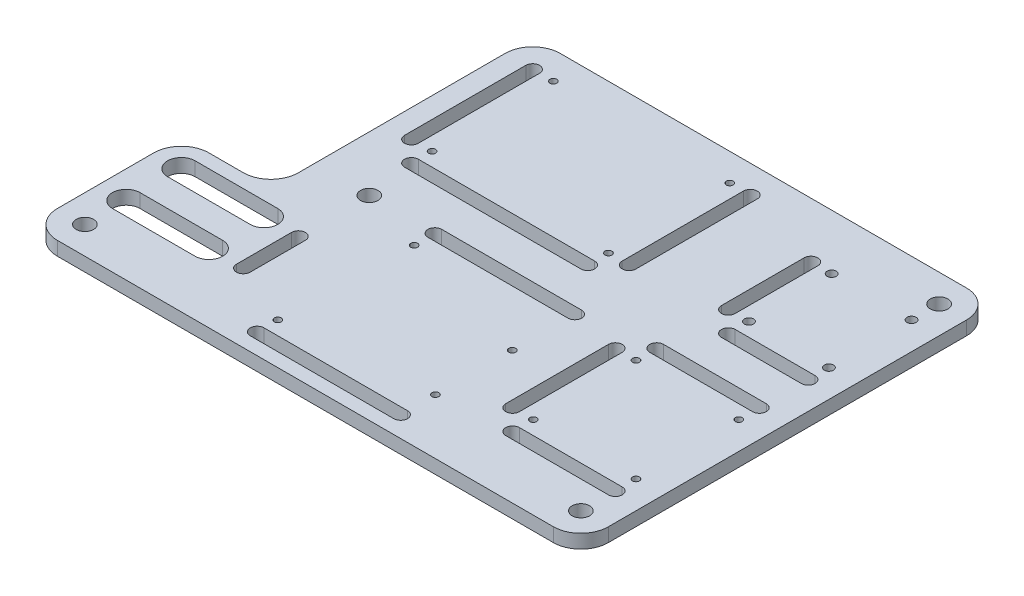
SolidWorks part; units mm, degrees
ref_plane "Front Plane" through (0, 0, 0) normal (0, 0, 1) x (1, 0, 0)
ref_plane "Top Plane" through (0, 0, 0) normal (0, 1, 0) x (1, 0, 0)
ref_plane "Right Plane" through (0, 0, 0) normal (1, 0, 0) x (0, 0, -1)
sketch "Sketch1" plane through (0, 0, 0) normal (0, 1, 0) x (1, 0, 0)
  line L1 (-90, -75) -> (90, -75)
  line L2 (-100, -65) -> (-100, 65)
  line L3 (-90, 75) -> (90, 75)
  line L4 (100, -65) -> (100, 65)
  line L5 (-100, -75) -> (100, 75) construction
  line L6 (-100, 75) -> (100, -75) construction
  arc A0 (90, -75) -> (100, -65) centre (90, -65) ccw
  arc A1 (-90, -75) -> (-100, -65) centre (-90, -65) cw
  arc A2 (-100, 65) -> (-90, 75) centre (-90, 65) cw
  arc A3 (90, 75) -> (100, 65) centre (90, 65) cw
  point P1 (0, 0)
  dimension "D3" = 10
  dimension "D1" = 200
  dimension "D2" = 150
extrude "Boss-Extrude1" add sketch "Sketch1" along normal blind 5 contours L2 A2 L3 A3 L4 A0 L1 A1
hole_wizard "arduino uno holes" positions "Sketch3" profile "Sketch2" tap size "M3x0.5" standard "ANSI Metric" end condition through all
sketch "Sketch3" plane through (0, 5, 0) normal (0, 1, 0) x (1, 0, 0)
  line L0 (-90, -75) -> (90, -75) construction
  line L1 (-100, -65) -> (-100, 65) construction
  point P0 (27.1, -27)
  point P2 (27.1, -54.9)
  point P4 (-23.7, -11.8)
  point P6 (-25, -60)
  dimension "D1" = 27.9
  dimension "D2" = 15.2
  dimension "D3" = 50.8
  dimension "D4" = 1.3
  dimension "D5" = 5.1
  dimension "D6" = 15
  dimension "D7" = 75
sketch "Sketch2" plane through (27.1, 5, 27) normal (1, 0, 0) x (0, 0, 1)
  line L0 (0, 0) -> (0, 5)
  line L1 (0, 5) -> (1.25, 5)
  line L2 (1.25, 5) -> (1.25, 0)
  line L5 (1.25, 0) -> (0, 0)
  line L11 (0, -6.35) -> (0, 107.95) construction
  dimension "Thru Tap Drill Dia." = 2.5
  dimension "Thru Tap Drill Depth" = 5
cosmetic thread "Hole Thread1" parameters "D2"=3
cosmetic thread "Hole Thread2" parameters "D2"=3
cosmetic thread "Hole Thread3" parameters "D2"=3
cosmetic thread "Hole Thread4" parameters "D2"=3
hole_wizard "l298n holes" positions "Sketch16" profile "Sketch17" tap size "M3x0.5" standard "ANSI Metric" end condition through all
sketch "Sketch16" plane through (0, 5, 0) normal (0, 1, 0) x (1, 0, 0)
  line L0 (100, -65) -> (100, 65) construction
  line L1 (-90, -75) -> (90, -75) construction
  point P0 (52.7, -45)
  point P6 (90, -45)
  point P7 (90, -7.7)
  point P8 (52.7, -7.7)
  dimension "D3" = 10
  dimension "D4" = 30
  dimension "D5" = 37.3
  dimension "D6" = 37.3
  dimension "D1" = 2
  dimension "D2" = 2
sketch "Sketch17" plane through (52.7, 5, 45) normal (1, 0, 0) x (0, 0, 1)
  line L0 (0, 0) -> (0, 5)
  line L1 (0, 5) -> (1.25, 5)
  line L2 (1.25, 5) -> (1.25, 0)
  line L5 (1.25, 0) -> (0, 0)
  line L11 (0, -6.35) -> (0, 107.95) construction
  dimension "Thru Tap Drill Dia." = 2.5
  dimension "Thru Tap Drill Depth" = 5
cosmetic thread "Hole Thread25" parameters "D2"=3
cosmetic thread "Hole Thread26" parameters "D2"=3
cosmetic thread "Hole Thread27" parameters "D2"=3
cosmetic thread "Hole Thread28" parameters "D2"=3
hole_wizard "protoboard holes" positions "Sketch20" profile "Sketch21" tap size "M3x0.5" standard "ANSI Metric" end condition through all
sketch "Sketch20" plane through (0, 5, 0) normal (0, 1, 0) x (1, 0, 0)
  line L0 (-90, 75) -> (90, 75) construction
  line L1 (-100, -65) -> (-100, 65) construction
  point P0 (-50, 21)
  point P6 (14, 21)
  point P7 (14, 65)
  point P8 (-50, 65)
  dimension "D3" = 10
  dimension "D4" = 50
  dimension "D5" = 64
  dimension "D6" = 44
  dimension "D1" = 2
  dimension "D2" = 2
sketch "Sketch21" plane through (-50, 5, -21) normal (1, 0, 0) x (0, 0, 1)
  line L0 (0, 0) -> (0, 5)
  line L1 (0, 5) -> (1.25, 5)
  line L2 (1.25, 5) -> (1.25, 0)
  line L5 (1.25, 0) -> (0, 0)
  line L11 (0, -6.35) -> (0, 107.95) construction
  dimension "Thru Tap Drill Dia." = 2.5
  dimension "Thru Tap Drill Depth" = 5
cosmetic thread "Hole Thread37" parameters "D2"=3
cosmetic thread "Hole Thread38" parameters "D2"=3
cosmetic thread "Hole Thread39" parameters "D2"=3
cosmetic thread "Hole Thread40" parameters "D2"=3
hole_wizard "l-bracket holes" positions "Sketch22" profile "Sketch23" tap size "M4x0.7" standard "ANSI Metric" end condition through all
sketch "Sketch22" plane through (0, 5, 0) normal (0, 1, 0) x (1, 0, 0)
  line L0 (-90, 75) -> (90, 75) construction
  line L1 (100, -65) -> (100, 65) construction
  point P12 (61, 55)
  point P19 (90, 55)
  point P20 (90, 25)
  point P21 (61, 25)
  dimension "D1" = 2
  dimension "D2" = 2
  dimension "D3" = 20
  dimension "D4" = 10
sketch "Sketch23" plane through (61, 5, -55) normal (1, 0, 0) x (0, 0, 1)
  line L0 (0, 0) -> (0, 5)
  line L1 (0, 5) -> (1.65, 5)
  line L2 (1.65, 5) -> (1.65, 0)
  line L5 (1.65, 0) -> (0, 0)
  line L11 (0, -6.35) -> (0, 107.95) construction
  dimension "Thru Tap Drill Dia." = 3.3
  dimension "Thru Tap Drill Depth" = 5
cosmetic thread "Hole Thread41" parameters "D2"=4
cosmetic thread "Hole Thread42" parameters "D2"=4
cosmetic thread "Hole Thread43" parameters "D2"=4
cosmetic thread "Hole Thread44" parameters "D2"=4
sketch "Sketch24" plane through (0, 5, 0) normal (0, 1, 0) x (1, 0, 0)
  line L0 (-60, -30) -> (-90, -30) construction
  line L1 (-60, -35) -> (-90, -35)
  line L2 (-60, -25) -> (-90, -25)
  line L3 (-100, -65) -> (-100, 65) construction
  line L4 (-60, -50) -> (-90, -50) construction
  line L5 (-60, -45) -> (-90, -45)
  line L6 (-60, -55) -> (-90, -55)
  line L7 (-90, -75) -> (90, -75) construction
  arc A0 (-60, -35) -> (-60, -25) centre (-60, -30) ccw
  arc A1 (-90, -25) -> (-90, -35) centre (-90, -30) ccw
  arc A2 (-60, -45) -> (-60, -55) centre (-60, -50) cw
  arc A3 (-90, -55) -> (-90, -45) centre (-90, -50) cw
  point P2 (-75, -30)
  point P7 (-95, -30)
  point P8 (-55, -30)
  point P11 (-75, -50)
  dimension "D1" = 10
  dimension "D2" = 40
  dimension "D4" = 20
  dimension "D3" = 5
  dimension "D5" = 10
extrude "power block slots" cut sketch "Sketch24" against normal through all
sketch "Sketch26" plane through (0, 5, 0) normal (0, 1, 0) x (1, 0, 0)
  line L0 (-50, 13.5) -> (14, 13.5) construction
  line L1 (-50, 16) -> (14, 16)
  line L2 (-50, 11) -> (14, 11)
  line L3 (21.5, 65) -> (21.5, 21) construction
  line L4 (24, 65) -> (24, 21)
  line L5 (19, 65) -> (19, 21)
  line L6 (53.5, 55) -> (53.5, 25) construction
  line L7 (56, 55) -> (56, 25)
  line L8 (51, 55) -> (51, 25)
  line L9 (61, 17.5) -> (90, 17.5) construction
  line L10 (61, 20) -> (90, 20)
  line L11 (61, 15) -> (90, 15)
  line L12 (52.7, -0.2) -> (90, -0.2) construction
  line L13 (52.7, 2.3) -> (90, 2.3)
  line L14 (52.7, -2.7) -> (90, -2.7)
  line L15 (45.2, -7.7) -> (45.2, -45) construction
  line L16 (47.7, -7.7) -> (47.7, -45)
  line L17 (42.7, -7.7) -> (42.7, -45)
  line L18 (-25, -67.5) -> (27.1, -67.5) construction
  line L19 (-25, -65) -> (27.1, -65)
  line L20 (-25, -70) -> (27.1, -70)
  line L21 (-47.5, -30) -> (-47.5, -50) construction
  line L22 (-45, -30) -> (-45, -50)
  line L23 (-50, -30) -> (-50, -50)
  line L24 (-23.7, -4.3) -> (27.1, -4.3) construction
  line L25 (-23.7, -1.8) -> (27.1, -1.8)
  line L26 (-23.7, -6.8) -> (27.1, -6.8)
  line L27 (-57.5, 65) -> (-57.5, 21) construction
  line L28 (-55, 65) -> (-55, 21)
  line L29 (-60, 65) -> (-60, 21)
  line L30 (90, -52.5) -> (52.7, -52.5) construction
  line L31 (90, -55) -> (52.7, -55)
  line L32 (90, -50) -> (52.7, -50)
  arc A0 (-50, 16) -> (-50, 11) centre (-50, 13.5) ccw
  arc A1 (14, 11) -> (14, 16) centre (14, 13.5) ccw
  circle A2 centre (14, 21) radius 1.25 construction
  arc A3 (24, 65) -> (19, 65) centre (21.5, 65) ccw
  arc A4 (19, 21) -> (24, 21) centre (21.5, 21) ccw
  arc A5 (56, 55) -> (51, 55) centre (53.5, 55) ccw
  arc A6 (51, 25) -> (56, 25) centre (53.5, 25) ccw
  circle A7 centre (61, 25) radius 1.65 construction
  arc A8 (61, 20) -> (61, 15) centre (61, 17.5) ccw
  arc A9 (90, 15) -> (90, 20) centre (90, 17.5) ccw
  circle A10 centre (90, 25) radius 1.65 construction
  arc A11 (52.7, 2.3) -> (52.7, -2.7) centre (52.7, -0.2) ccw
  arc A12 (90, -2.7) -> (90, 2.3) centre (90, -0.2) ccw
  arc A13 (47.7, -7.7) -> (42.7, -7.7) centre (45.2, -7.7) ccw
  arc A14 (42.7, -45) -> (47.7, -45) centre (45.2, -45) ccw
  circle A15 centre (52.7, -45) radius 1.25 construction
  arc A16 (-25, -65) -> (-25, -70) centre (-25, -67.5) ccw
  arc A17 (27.1, -70) -> (27.1, -65) centre (27.1, -67.5) ccw
  arc A18 (-45, -30) -> (-50, -30) centre (-47.5, -30) ccw
  arc A19 (-50, -50) -> (-45, -50) centre (-47.5, -50) ccw
  circle A20 centre (-25, -60) radius 1.25 construction
  arc A21 (-60, -35) -> (-60, -25) centre (-60, -30) ccw construction
  circle A22 centre (-23.7, -11.8) radius 1.25 construction
  arc A23 (-55, 65) -> (-60, 65) centre (-57.5, 65) ccw
  arc A24 (-60, 21) -> (-55, 21) centre (-57.5, 21) ccw
  circle A25 centre (52.7, -7.7) radius 1.25 construction
  arc A26 (-23.7, -1.8) -> (-23.7, -6.8) centre (-23.7, -4.3) ccw
  arc A27 (27.1, -6.8) -> (27.1, -1.8) centre (27.1, -4.3) ccw
  circle A28 centre (-50, 21) radius 1.25 construction
  arc A29 (90, -55) -> (90, -50) centre (90, -52.5) ccw
  arc A30 (52.7, -50) -> (52.7, -55) centre (52.7, -52.5) ccw
  circle A31 centre (90, -45) radius 1.25 construction
  point P2 (-18, 13.5)
  point P11 (21.5, 43)
  point P18 (53.5, 40)
  point P27 (75.5, 17.5)
  point P36 (71.35, -0.2)
  point P41 (45.2, -26.35)
  point P52 (1.05, -67.5)
  point P59 (-47.5, -40)
  point P72 (1.7, -4.3)
  point P80 (-55, -30)
  point P83 (-57.5, 43)
  point P92 (71.35, -52.5)
  dimension "D1" = 5
  dimension "D2" = 5
  dimension "D3" = 5
  dimension "D4" = 5
  dimension "D5" = 5
  dimension "D6" = 5
  dimension "D7" = 5
  dimension "D8" = 5
  dimension "D9" = 5
  dimension "D10" = 5
  dimension "D11" = 5
  dimension "D12" = 5
  dimension "D15" = 5
  dimension "D16" = 5
  dimension "D17" = 5
  dimension "D18" = 5
  dimension "D13" = 5
  dimension "D14" = 5
  dimension "D19" = 5
  dimension "D20" = 5
  dimension "D21" = 5
  dimension "D22" = 5
extrude "cable management slots" cut sketch "Sketch26" against normal through all
sketch "Sketch27" plane through (0, 5, 0) normal (0, 1, 0) x (1, 0, 0)
  line L0 (-67.5, 65) -> (-67.5, -10)
  line L1 (-77.5, -20) -> (-90, -20)
  line L2 (-57.5, 75) -> (-90, 75)
  line L3 (-100, -65) -> (-100, 65) construction
  line L4 (-100, -30) -> (-100, 65)
  circle A0 centre (-57.5, 65) radius 10
  circle A1 centre (-90, -30) radius 10
  arc A2 (-67.5, -10) -> (-77.5, -20) centre (-77.5, -10) cw
  arc A3 (-90, 75) -> (-100, 65) centre (-90, 65) ccw construction
  arc A4 (-90, 75) -> (-100, 65) centre (-90, 65) ccw
  dimension "D1" = 10
extrude "Cut-Extrude3" cut sketch "Sketch27" against normal blind 10 contours L2 A4 L4 A1 L1 A2 L0 A0 region at (-83.7189, 5, -27.4689)
hole_wizard "wall-mounting holes" positions "Sketch28" profile "Sketch29" hole size "1/4" standard "ANSI Inch" end condition through all
sketch "Sketch28" plane through (0, 5, 0) normal (0, 1, 0) x (1, 0, 0)
  point P0 (-90, -65)
  point P3 (90, -65)
  point P6 (90, 65)
  point P9 (-47.5, -4.3)
sketch "Sketch29" plane through (-90, 5, 65) normal (1, 0, 0) x (0, 0, 1)
  line L0 (0, 0) -> (0, 5)
  line L1 (0, 5) -> (3.175, 5)
  line L2 (3.175, 5) -> (3.175, 0)
  line L5 (3.175, 0) -> (0, 0)
  line L11 (0, -6.35) -> (0, 107.95) construction
  dimension "Thru Hole Dia." = 6.35
  dimension "Thru Hole Depth" = 5
equation "\"w\"= 200"
equation "\"D1@Sketch1\"=\"w\""
equation "\"h\"= 150"
equation "\"D2@Sketch1\"=\"h\""
equation "\"th\"=5"
equation "\"D1@Boss-Extrude1\"=\"th\""
equation "\"D5@Sketch16\"=\"D6@Sketch16\""
equation "\"slot_w\"= 5"
equation "\"D11@Sketch26\"=\"slot_w\""
equation "\"D9@Sketch26\"=\"slot_w\""
equation "\"D5@Sketch26\"=\"slot_w\""
equation "\"D7@Sketch26\"=\"slot_w\""
equation "\"D2@Sketch26\"=\"slot_w\""
equation "\"D3@Sketch26\"=\"slot_w\""
equation "\"D15@Sketch26\"=\"slot_w\""
equation "\"D17@Sketch26\"=\"slot_w\""
equation "\"slot_dist\"= 5"
equation "\"D18@Sketch26\"=\"slot_dist\""
equation "\"D12@Sketch26\"=\"slot_dist\""
equation "\"D10@Sketch26\"=\"slot_dist\""
equation "\"D16@Sketch26\"=\"slot_dist\""
equation "\"D8@Sketch26\"=\"slot_dist\""
equation "\"D6@Sketch26\"=\"slot_dist\""
equation "\"D4@Sketch26\"=\"slot_dist\""
equation "\"D1@Sketch26\"=\"slot_dist\""
equation "\"D14@Sketch26\"=\"slot_dist\""
equation "\"D13@Sketch26\"=\"slot_w\""
equation "\"D19@Sketch26\"=\"slot_w\""
equation "\"D20@Sketch26\"=\"slot_dist\""
equation "\"D21@Sketch26\"=\"slot_w\""
equation "\"D22@Sketch26\"=\"slot_dist\""
